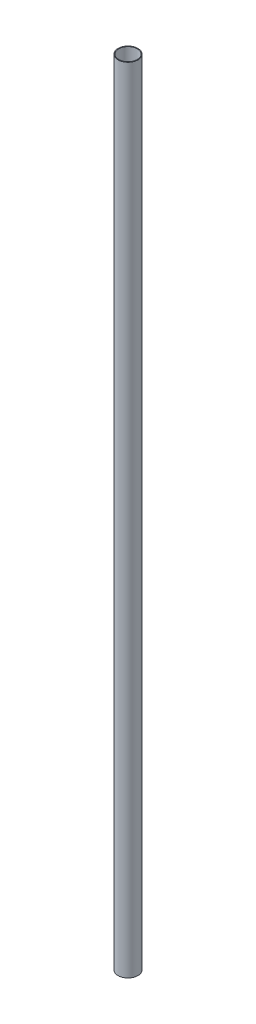
SolidWorks part; units mm, degrees
ref_plane "Front" through (0, 0, 0) normal (0, 0, 1) x (1, 0, 0)
ref_plane "Top" through (0, 0, 0) normal (0, 1, 0) x (1, 0, 0)
ref_plane "Right" through (0, 0, 0) normal (1, 0, 0) x (0, 0, -1)
sketch "Body Driving Dimensions" plane through (0, 0, 0) normal (0, 0, 1) x (1, 0, 0)
  line L0 (0, 0) -> (55.1074, -64.7161)
  line L1 (55.1074, -64.7161) -> (0, -241.3179)
  line L2 (0, -241.3179) -> (-55.1074, -64.7161)
  line L3 (-55.1074, -64.7161) -> (0, 0)
  line L4 (0, 0) -> (0, -36.971) construction
  line L5 (0, 0) -> (149.36, 95.9979)
  line L6 (149.36, 95.9979) -> (55.1074, -64.7161)
  line L7 (0, 0) -> (-100.024, 45.7734)
  line L8 (-100.024, 45.7734) -> (-55.1074, -64.7161)
  line L9 (149.36, 95.9979) -> (256.2032, 164.669) construction
  line L10 (-100.024, 45.7734) -> (-215.514, 98.6245) construction
  line L11 (149.36, 95.9979) -> (149.36, 64.3258) construction
  line L12 (-100.024, 45.7734) -> (-100.024, 14.1013) construction
  line L13 (0, 0) -> (-98.8336, -98.8336) construction
  line L14 (0, 0) -> (98.8336, -98.8336) construction
  line L15 (-132.0501, 46.6827) -> (-121.647, 69.4154)
  line L16 (179.583, 103.5357) -> (168.7694, 120.3603)
  point P3 (-113.6636, 52.0153)
  point P16 (-126.8486, 58.049)
  point P20 (174.1762, 111.948)
  point P21 (161.9784, 104.1081)
  point P22 (0, 0)
  dimension "D1" = 45
  dimension "D2" = 45
  dimension "D3" = 185
  dimension "D4" = 85
  dimension "D5" = 177.55
  dimension "D6" = 110
  dimension "D7" = 122.73
  dimension "D8" = 114.59
  dimension "D9" = 25
  dimension "D11" = 20
  dimension "D10" = 15
  dimension "D13" = 14.5
  dimension "D12" = 15
  dimension "D14" = 14.5
sketch "Sketch38" [suppressed] plane through (0, 0, 0) normal (0, 0, 1) x (1, 0, 0)
  line L0 (-100.024, 45.7734) -> (-215.514, 98.6245) construction
  line L1 (-103.9479, 52.3387) -> (-98.4151, 47.687)
  line L2 (-107.5573, 44.4513) -> (-100.4204, 43.3051)
  circle A0 centre (-100.024, 45.7734) radius 1
  circle A1 centre (-106.8438, 48.8943) radius 3
  circle A2 centre (-106.8438, 48.8943) radius 4.5 construction
  circle A3 centre (-100.024, 45.7734) radius 2.5 construction
  arc A4 (-98.4151, 47.687) -> (-100.4204, 43.3051) centre (-100.024, 45.7734) cw
  arc A5 (-103.9479, 52.3387) -> (-107.5573, 44.4513) centre (-106.8438, 48.8943) ccw
  dimension "D1" = 2
  dimension "D2" = 6
  dimension "D3" = 9
  dimension "D4" = 5
  dimension "D5" = 7.5
sketch "Sketch29" plane through (0, 0, 0) normal (0, 0, 1) x (1, 0, 0)
  line L0 (-132.0501, 46.6827) -> (-121.647, 69.4154) construction
  line L1 (-138.8699, 49.8036) -> (-128.4669, 72.5363)
  line L2 (-125.2303, 43.5618) -> (-114.8272, 66.2945)
  arc A0 (-138.8699, 49.8036) -> (-125.2303, 43.5618) centre (-132.0501, 46.6827) ccw
  arc A1 (-114.8272, 66.2945) -> (-128.4669, 72.5363) centre (-121.647, 69.4154) ccw
  point P4 (-126.8486, 58.049)
  dimension "D1" = 15
sketch "Sketch1" plane through (0, 0, 0) normal (0, 0, 1) x (1, 0, 0)
  line L0 (-55.1074, -64.7161) -> (0, -241.3179) construction
  line L1 (-47.9478, -62.4821) -> (7.1595, -239.0838)
  line L2 (-62.2669, -66.9502) -> (-7.1595, -243.552)
  circle A0 centre (-55.1074, -64.7161) radius 3.5
  circle A1 centre (0, -241.3179) radius 3.5
  arc A2 (-47.9478, -62.4821) -> (-62.2669, -66.9502) centre (-55.1074, -64.7161) ccw
  arc A3 (-7.1595, -243.552) -> (7.1595, -239.0838) centre (0, -241.3179) ccw
  point P6 (-27.5537, -153.017)
  dimension "D1" = 7
  dimension "D2" = 7.5
extrude "Tibya" [suppressed] add sketch "Sketch1" along normal blind 6
sketch "Sketch2" [suppressed] plane through (0, 0, 0) normal (0, 0, 1) x (1, 0, 0)
  line L0 (0, 0) -> (85, 0) construction
  line L1 (0, 0) -> (55.1074, -64.7161) construction
  line L2 (85.6537, 7.4715) -> (16.0331, 13.5625)
  line L4 (85.6537, -7.4715) -> (16.0331, -13.5625)
  circle A0 centre (0, 0) radius 17.5 construction
  circle A1 centre (0, 17.5) radius 1.65
  circle A2 centre (-17.5, 0) radius 1.65
  circle A3 centre (17.5, 0) radius 1.65
  circle A4 centre (0, -17.5) radius 1.65
  circle A5 centre (85, 0) radius 3.5
  circle A6 centre (85, 0) radius 7.5 construction
  circle A7 centre (0, 0) radius 21 construction
  arc A8 (85.6537, 7.4715) -> (85.6537, -7.4715) centre (85, 0) cw
  arc A9 (16.0331, 13.5625) -> (16.0331, -13.5625) centre (0, 0) ccw
  circle A10 centre (0, 0) radius 7
  dimension "D1" = 3.3
  dimension "D2" = 35
  dimension "D3" = 7
  dimension "D4" = 42
  dimension "D5" = 15
  dimension "D6" = 14
  dimension "D7" = 5
extrude "Boss-Extrude2" [suppressed] add sketch "Sketch2" along normal blind 6
fillet "Fillet1" [suppressed] radius 5
sketch "Sketch4" [suppressed] plane through (0, 0, 0) normal (1, 0, 0) x (0, 0, -1)
  line L0 (27.75, 0) -> (-27.75, 0)
  point P4 (0, 0)
  dimension "D1" = 55.5
sketch "Sketch5" plane through (0, 0, 0) normal (0, 1, 0) x (1, 0, 0)
  circle A0 centre (0, 0) radius 3.5
  circle A2 centre (0, 0) radius 3.25
  dimension "D1" = 7
  dimension "D2" = 0.25
extrude "Boss-Extrude3" add sketch "Sketch5" against normal blind 278
sketch "Sketch6" plane through (0, 0, 0) normal (0, 0, 1) x (1, 0, 0)
  line L0 (-37.2741, 76.3914) -> (-100.024, 45.7734) construction
  line L1 (-6.1172, 84.7796) -> (149.36, 95.9979) construction
  circle A0 centre (0, 0) radius 85 construction
  circle A1 centre (0, 0) radius 177.55 construction
  circle A2 centre (0, 0) radius 110 construction
sketch "Sketch8" plane through (0, 0, 0) normal (0, 0, 1) x (1, 0, 0)
  line L0 (0, 0) -> (0, 150) construction
  line L3 (0, 150) -> (0, 110) construction
  line L4 (0, 0) -> (-128.3471, 58.7348) construction
  line L7 (0, 0) -> (-100.024, 45.7734) construction
  line L8 (-100.024, 45.7734) -> (-215.514, 98.6245) construction
  line L12 (40, 115) -> (-40, 115) construction
  line L13 (40, 65) -> (-40, 65) construction
  line L14 (-145.3668, 41.6144) -> (-126.5165, 82.8061)
  line L15 (-126.5165, 82.8061) -> (-63.7414, 54.0787)
  line L16 (0, 0) -> (182.2103, 117.1117) construction
  line L17 (-145.3668, 41.6144) -> (-54.9994, 0.26)
  line L18 (-50, 66.9886) -> (-50, 125)
  line L19 (-50, 125) -> (50, 125)
  line L20 (50, 125) -> (50, 66.9886)
  line L21 (194.8349, 98.301) -> (54.4084, 8.0449)
  line L23 (149.36, 95.9979) -> (256.2032, 164.669) construction
  line L24 (194.8349, 98.301) -> (170.3421, 136.4086)
  line L25 (170.3421, 136.4086) -> (55.4421, 62.5591)
  line L26 (179.583, 103.5357) -> (168.7694, 120.3603) construction
  circle A0 centre (0, 0) radius 55 construction
  circle A1 centre (0, 0) radius 177.55 construction
  circle A2 centre (0, 0) radius 45
  circle A4 centre (-40, 115) radius 2.65
  circle A5 centre (0, 0) radius 110 construction
  circle A6 centre (40, 115) radius 2.65
  circle A7 centre (0, 115) radius 2.65
  circle A8 centre (40, 65) radius 2.65
  circle A9 centre (0, 65) radius 2.65
  circle A10 centre (-40, 65) radius 2.65
  circle A11 centre (0, 0) radius 83.5911 construction
  arc A12 (-63.7414, 54.0787) -> (-50, 66.9886) centre (0, 0) cw
  arc A13 (-54.9994, 0.26) -> (54.4084, 8.0449) centre (0, 0) ccw
  arc A14 (50, 66.9886) -> (55.4421, 62.5591) centre (0, 0) cw
  point P12 (0, 177.55)
  point P17 (-135.9417, 62.2103)
  point P26 (0, 115)
  point P33 (0, 0)
  point P37 (0, 65)
  point P50 (182.5885, 117.3548)
  point P53 (0, 0)
  dimension "D2" = 110
  dimension "D3" = 90
  dimension "D10" = 5.3
  dimension "D16" = 40
  dimension "D4" = 65
  dimension "D5" = 45.3
  dimension "D6" = 10
  dimension "D7" = 45.3
  dimension "D8" = 10
  dimension "D9" = 10
  dimension "D11" = 80
  dimension "D12" = 50
  dimension "D13" = 40
  dimension "D14" = 10
  dimension "D15" = 10
sketch "Sketch17" [suppressed] plane through (0, 0, 0) normal (0, 0, 1) x (1, 0, 0)
  line L0 (0, 0) -> (-45, 0) construction
  line L1 (0, 0) -> (0, 45) construction
  line L2 (0, 0) -> (-35.3553, 35.3553) construction
  line L3 (0, 0) -> (0, 170) construction
  line L4 (54, 170) -> (-54, 170)
  line L5 (-54, 170) -> (-54, 0)
  line L6 (54, 0) -> (54, 170)
  line L7 (45, 162.5) -> (-45, 162.5) construction
  line L8 (45, 112.5) -> (-45, 112.5) construction
  circle A0 centre (0, 0) radius 45
  circle A1 centre (-35.3553, 35.3553) radius 1.65
  circle A2 centre (35.3553, 35.3553) radius 1.65
  circle A3 centre (35.3553, -35.3553) radius 1.65
  circle A4 centre (-35.3553, -35.3553) radius 1.65
  circle A5 centre (0, 0) radius 54 construction
  circle A6 centre (0, 162.5) radius 2.65
  arc A7 (-54, 0) -> (54, 0) centre (0, 0) ccw
  circle A8 centre (-45, 162.5) radius 2.65
  circle A9 centre (45, 162.5) radius 2.65
  circle A10 centre (-45, 112.5) radius 2.65
  circle A11 centre (-35.3553, 35.3553) radius 4 construction
  circle A12 centre (0, 112.5) radius 2.65
  circle A13 centre (45, 112.5) radius 2.65
  point P16 (0, 0)
  point P19 (0, 170)
  point P25 (0, 162.5)
  point P33 (0, 112.5)
  dimension "D1" = 90
  dimension "D4" = 3.3
  dimension "D6" = 170
  dimension "D9" = 5.3
  dimension "D11" = 8
  dimension "D7" = 50
  dimension "D2" = 45
  dimension "D3" = 50
  dimension "D8" = 90
  dimension "D10" = 7.5
  dimension "D5" = 4
extrude "Simple Side Plate" [suppressed] add sketch "Sketch17" along normal blind 6
fillet "Fillet7" [suppressed] radius 2.5
equation "\"l2\"= 185"
equation "\"D3@Body Driving Dimensions\" = \"l2\""
equation "\"l1\"= 85"
equation "\"D4@Body Driving Dimensions\" = \"l1\""
equation "\"s1r\"= 2.14212rad"
equation "\"s2r\"= - 2rad"
equation "\"offset\"= 10mm"
equation "\"s1_len\"= 0.08255m"
equation "\"s2_len\"= 0.015m"
equation "\"s1_anchor_dist\"= \"offset\" + \"l1\" + \"s1_len\""
equation "\"s2_anchor_dist\"= \"offset\" + \"l1\" + \"s2_len\"'this was: = \"offset\" + \"l1\" + \"s2_len\""
equation "\"D5@Body Driving Dimensions\" = \"s1_anchor_dist\""
equation "\"D6@Body Driving Dimensions\" = \"s2_anchor_dist\""
equation "\"D7@Body Driving Dimensions\" = \"s1r\""
equation "\"D8@Body Driving Dimensions\" =  - \"s2r\""
equation "\"carbon_fiber_plate_thickness\"=6"
equation "\"D1@Tibya\" = \"carbon_fiber_plate_thickness\""
equation "\"D1@Boss-Extrude2\"=\"carbon_fiber_plate_thickness\""
equation "\"motor_to_motor_spacing\"=55.5"
equation "\"D1@Sketch4\"=\"motor_to_motor_spacing\""
equation "\"D1@Boss-Extrude3\"=\"l1\"+\"l2\" + 8"
equation "\"D1\"= \"motor_to_motor_spacing\" + 30mm"
equation "\"D10@Body Driving Dimensions\"=\"offset\"+5mm"
